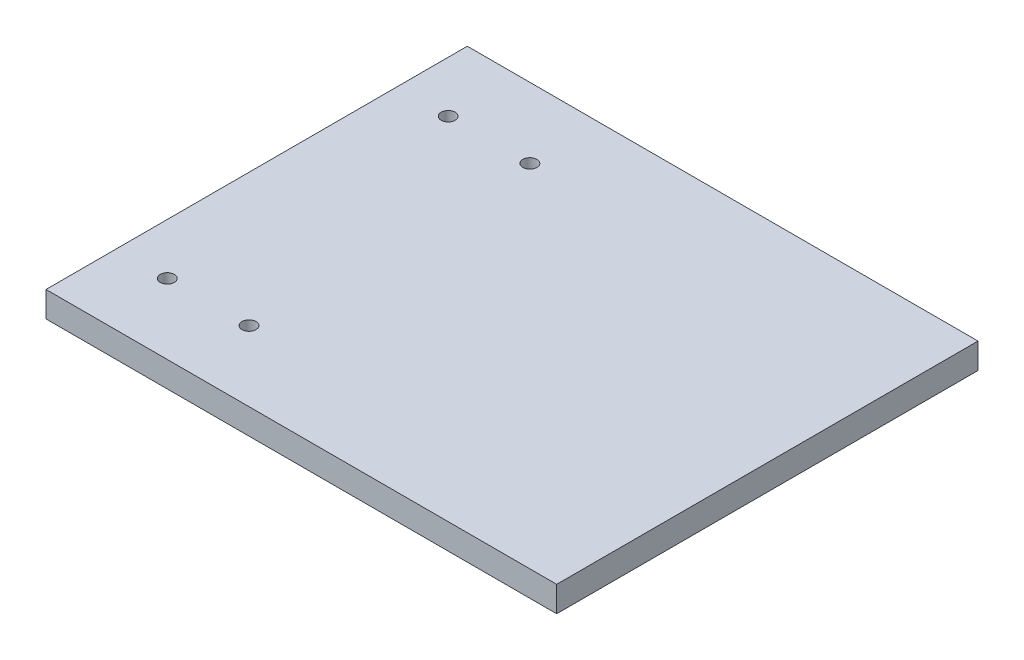
SolidWorks part; units mm, degrees
ref_plane "Front Plane" through (0, 0, 0) normal (0, 0, 1) x (1, 0, 0)
ref_plane "Top Plane" through (0, 0, 0) normal (0, 1, 0) x (1, 0, 0)
ref_plane "Right Plane" through (0, 0, 0) normal (1, 0, 0) x (0, 0, -1)
sketch "Sketch1" plane through (0, 0, 0) normal (0, 1, 0) x (1, 0, 0)
  line L0 (0, 0) -> (0, 165)
  line L1 (0, 165) -> (200, 165)
  line L2 (200, 165) -> (200, 0)
  line L3 (200, 0) -> (0, 0)
  circle A0 centre (20, 27.5) radius 2.75
  circle A1 centre (52, 27.5) radius 2.75
  circle A2 centre (20, 137.5) radius 2.75
  circle A3 centre (52, 137.5) radius 2.75
  point P13 (0, 0)
  point P14 (0, 0)
  point P15 (0, 0)
  point P16 (0, 0)
  dimension "D2" = 5.5
  dimension "D3" = 110
  dimension "D4" = 32
  dimension "D5" = 27.5
  dimension "D6" = 20
  dimension "D1" = 165
  dimension "D7" = 200
extrude "Boss-Extrude2" add sketch "Sketch1" along normal blind 10
